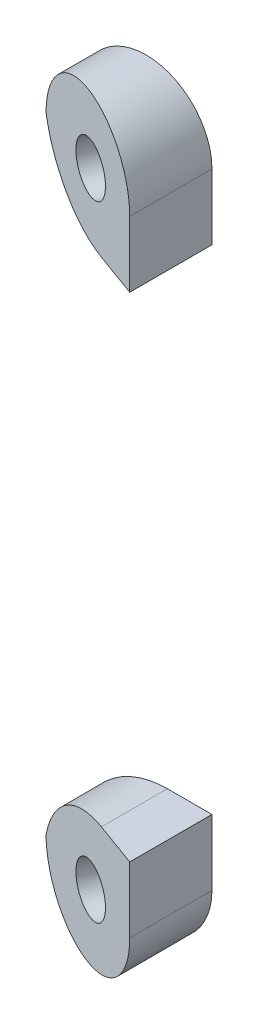
SolidWorks part; units mm, degrees
ref_plane "Front Plane" through (0, 0, 0) normal (0, 0, 1) x (1, 0, 0)
ref_plane "Top Plane" through (0, 0, 0) normal (0, 1, 0) x (1, 0, 0)
ref_plane "Right Plane" through (0, 0, 0) normal (1, 0, 0) x (0, 0, -1)
sketch "Sketch1" plane through (0, 0, 0) normal (0, 0, 1) x (1, 0, 0)
  line L0 (68.3946, 19) -> (68.3946, -19) construction
  line L1 (72.3946, 19) -> (72.3946, -19)
  line L2 (64.3946, 19) -> (64.3946, -19)
  line L3 (68.3946, 0) -> (0, 0) construction
  arc A0 (72.3946, 19) -> (64.3946, 19) centre (68.3946, 19) ccw
  arc A1 (64.3946, -19) -> (72.3946, -19) centre (68.3946, -19) ccw
  ellipse E0 centre (69.9909, 19) end of major axis (71.5871, 19) minor radius 1.5 (69.9909, 20.5) -> (69.9909, 17.5) ccw construction
  point P2 (68.3946, 0)
  dimension "D1" = 38
  dimension "D2" = 8
extrude "Boss-Extrude1" add sketch "Sketch1" along normal blind 5
sketch "Sketch2" plane through (0, 0, 0) normal (0, 1, 0) x (1, 0, 0)
  line L0 (72.3946, -5) -> (64.3946, -2.0882)
  line L1 (64.3946, -5) -> (64.3946, 0) construction
  line L2 (64.3946, -2.0882) -> (64.3946, -5)
  line L3 (64.3946, -5) -> (72.3946, -5)
  line L4 (44.9462, 18.6968) -> (85.353, 3.9899) construction
extrude "Cut-Extrude1" cut sketch "Sketch2" against normal through all both and the other way through all
sketch "Sketch3" plane through (6.8616, 0, -18.8521) normal (-0.342, 0, 0.9397) x (0.9397, 0, 0.342)
  circle A0 centre (65.7699, 19) radius 1.5 construction
  circle A1 centre (65.7699, -19) radius 1.5 construction
  circle A2 centre (65.7699, 19) radius 1.5
  circle A3 centre (65.7699, -19) radius 1.5
extrude "Cut-Extrude2" cut sketch "Sketch3" against normal blind 91
sketch "Sketch4" plane through (0, 0, 0) normal (0, 0, 1) x (1, 0, 0)
  line L0 (72.3946, -19) -> (72.3946, 19) construction
  line L1 (89.2769, -15) -> (55.5123, -15)
  line L2 (89.2769, -15) -> (89.2769, 15)
  line L3 (89.2769, 15) -> (55.5123, 15)
  line L4 (55.5123, -15) -> (55.5123, 15)
  line L5 (89.2769, -15) -> (55.5123, 15) construction
  line L6 (89.2769, 15) -> (55.5123, -15) construction
  point P0 (72.3946, 0)
  dimension "D1" = 30
split "Split1" trim tools "Sketch4" bodies to split 103 resulting bodies 104 105
fillet "Fillet1" radius 5.5 1 edges at (64.3946, 15, 1.0441)
fillet "Fillet2" radius 5.5 1 edges at (64.3946, -15, 1.0441)
